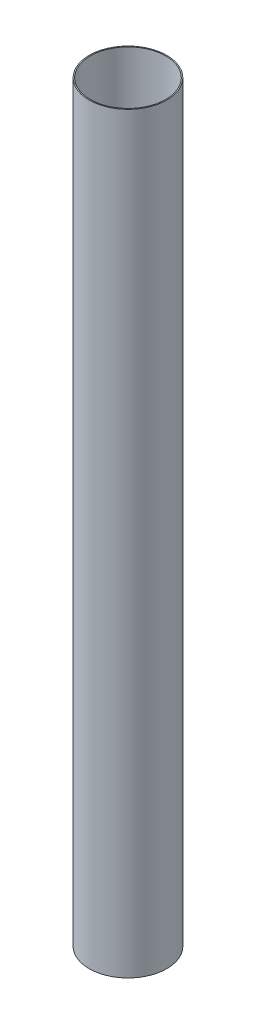
SolidWorks part; units mm, degrees
material "Hexcel AS4C (3000 Filaments)"
ref_plane "Front Plane" through (0, 0, 0) normal (0, 0, 1) x (1, 0, 0)
ref_plane "Top Plane" through (0, 0, 0) normal (0, 1, 0) x (1, 0, 0)
ref_plane "Right Plane" through (0, 0, 0) normal (1, 0, 0) x (0, 0, -1)
sketch "Sketch1" plane through (0, 0, 0) normal (0, 1, 0) x (1, 0, 0)
  circle A0 centre (0, 0) radius 76.454
  circle A1 centre (0, 0) radius 78.5876
  dimension "D1" = 152.908
  dimension "D2" = 157.1752
extrude "Boss-Extrude1" add sketch "Sketch1" along normal blind 1524
